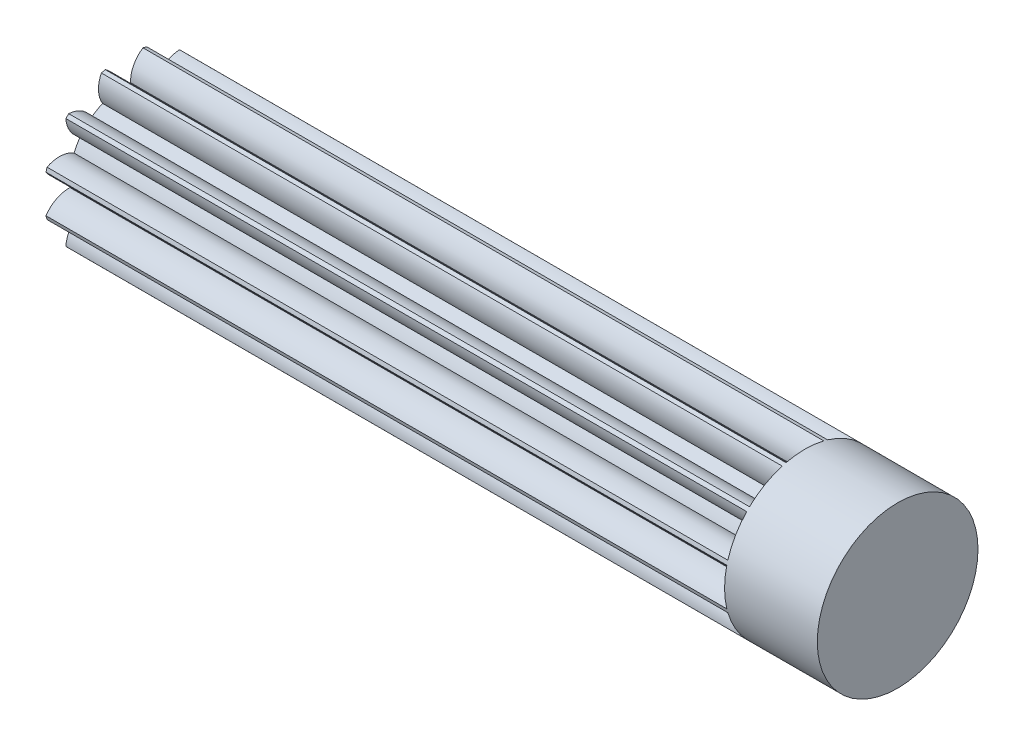
SolidWorks part; units mm, degrees
ref_plane "Plane1" through (0, 0, 0) normal (0, 0, 1) x (1, 0, 0)
ref_plane "Plane2" through (0, 0, 0) normal (0, 1, 0) x (1, 0, 0)
ref_plane "Plane3" through (0, 0, 0) normal (1, 0, 0) x (0, 0, -1)
sketch "HoldingSke" plane through (0, 0, 0) normal (0, 1, 0) x (1, 0, 0)
  line L0 (0, 0) -> (0.9781, -0.2079)
  line L1 (-15, 0) -> (100, 0) construction
  line L2 (0, 0) -> (-2.1039, 2.3779)
  line L3 (0, 0) -> (-11.863, 4.5341)
  line L4 (0, 0) -> (8.4473, 1.7955)
  line L5 (0, 0) -> (-46.8476, -17.4728)
  line L6 (0, 0) -> (-9.9476, -6.7116)
  line L7 (-2.1039, 2.3779) -> (8.6586, 51.2059)
  line L8 (-76.2, 54.61) -> (-76.1, 54.61)
  line L9 (-71.009, 38.7566) -> (-53.1078, 45.2721)
  line L10 (-76.2, 71.12) -> (104.1128, 71.12)
  line L11 (0, 0) -> (-12, 0)
  line L12 (-76.2, 101.6) -> (-76.162, 101.6)
  line L13 (24.9733, 27.94) -> (52.9518, 28.4284)
  line L14 (24.9733, 27.94) -> (24.9743, 27.94)
  line L15 (24.9733, 27.94) -> (100.4006, 29.5858)
  line L16 (-63.627, -1) -> (-12.827, -1)
  circle A0 centre (0, 0) radius 0.4
  circle A1 centre (0, 0) radius 4.749
  circle A2 centre (0, 0) radius 37.5
  circle A3 centre (0, 0) radius 0.4
  dimension "MHD" = 9.498
  dimension "Hub_dia" = 75
  dimension "Bore" = 0.8
  dimension "MBD" = 0.8
  dimension "Num_teeth" = 12
  dimension "Pitch" = 1
  dimension "Overall_len" = 50
  dimension "Show_teeth" = 12
  dimension "Thickness" = 12
  dimension "OAL" = 50.0001
  dimension "T_dim" = 0.1
  dimension "Ap" = 20
  dimension "H" = 19.05
  dimension "Pitch_radius" = 180.3128
  dimension "Width" = 12
  dimension "Backlash" = 0.038
  dimension "Addendum_fac" = 1
  dimension "Dedendum_fac" = 1.25
  dimension "Clearance_fac" = 0.25
  dimension "Dedendum_add" = 0.001
  dimension "Module" = 1
sketch "BasProSke" plane through (0, 0, 0) normal (0, 1, 0) x (1, 0, 0)
  line L0 (-10, 0) -> (60, 0) construction
  line L1 (0, 0) -> (0, 7)
  line L2 (0, 0) -> (59.315, 0)
  line L3 (59.315, 0) -> (59.315, 7)
  line L4 (59.315, 7) -> (0, 7)
  dimension "Thickness" = 59.315
  dimension "Diameter" = 14
revolve "Base-Revolve" add sketch "BasProSke" angle 360 about L0
sketch "TooCutSke" plane through (0, 0, 0) normal (1, 0, 0) x (0, 0, -1)
  line L1 (0, 0) -> (0, 107) construction
  line L2 (0, 0) -> (-0.8496, 5.9395) construction
  line L3 (0, 0) -> (-3.0836, 11.5081) construction
  line L4 (-0.8496, 5.9395) -> (-1.5418, 5.7541) construction
  arc A0 (0.5622, 4.7156) -> (-0.5622, 4.7156) centre (0, 0) ccw
  arc A1 (1.6729, 6.8233) -> (-1.6729, 6.8233) centre (0, 0) ccw
  circle A2 centre (0, 0) radius 6 construction
  circle A3 centre (0, 0) radius 5.6382 construction
  arc A4 (-0.5622, 4.7156) -> (-1.6729, 6.8233) centre (-2.9608, 4.7982) ccw
  arc A5 (1.6729, 6.8233) -> (0.5622, 4.7156) centre (2.9608, 4.7982) ccw
  dimension "Root_dia" = 9.498
  dimension "Overcut_dia" = 14.0508
  dimension "Pitch_dia" = 12
  dimension "Base_dia" = 11.2763
  dimension "Flank_rad" = 2.4
  dimension "Half_ang" = 15
  dimension "Half_CT" = 0.7167
extrude "ToothCut" cut sketch "TooCutSke" along normal through all
fillet "Breaks" [suppressed] radius 0.02 tangent propagation no
fillet "RootFillets" [suppressed] radius 0.251
pattern_circular "TeethCuts" count 12 every 30 about axis through (-10, 0, 0) along (1, 0, 0) of "ToothCut", "RootFillets", "Breaks"
sketch "HubNeaOneSke" plane through (0, 0, 0) normal (-1, 0, 0) x (0, 0, 1)
  circle A0 centre (0, 0) radius 4.749
  dimension "Diameter" = 9.498
extrude "HubNearOne" [suppressed] add sketch "HubNeaOneSke" along normal blind 10.4351
sketch "HubNeaBotSke" plane through (0, 0, 0) normal (-1, 0, 0) x (0, 0, 1)
  circle A0 centre (0, 0) radius 4.749
  dimension "Diameter" = 9.498
extrude "HubNearBoth" [suppressed] add sketch "HubNeaBotSke" along normal blind 5.2175
ref_plane "FarPln" through (59.315, 0, 0) normal (1, 0, 0) x (0, 0, -1)
sketch "HubFarSke" plane through (59.315, 0, 0) normal (1, 0, 0) x (0, 0, -1)
  circle A0 centre (0, 0) radius 4.749
  dimension "Diameter" = 9.498
extrude "HubFar" [suppressed] add sketch "HubFarSke" along normal blind 5.2175
sketch "BorSke" plane through (0, 0, 0) normal (1, 0, 0) x (0, 0, -1)
  circle A0 centre (0, 0) radius 0.4
  dimension "Diameter" = 0.8
extrude "Bore" cut sketch "BorSke" along normal mid plane 100.0001
sketch "KeySke" plane through (0, 0, 0) normal (1, 0, 0) x (0, 0, -1)
  line L0 (-0.05, 0) -> (-0.05, 0.5)
  line L1 (-0.05, 0.5) -> (0.05, 0.5)
  line L2 (0.05, 0.5) -> (0.05, 0)
  line L3 (0, 0) -> (0, 34) construction
  line L4 (-0.05, 0) -> (0.05, 0)
  dimension "Offset" = 0.5
  dimension "Width" = 0.1
extrude "Keyway" [suppressed] cut sketch "KeySke" along normal mid plane 100.0001
pattern_circular "Keyway2" [suppressed] count 2 every 90 about axis through (-10, 0, 0) along (1, 0, 0) reverse direction yes
sketch "Sketch1" plane through (0, 0, 0) normal (-1, 0, 0) x (0, 0, 1)
  circle A0 centre (0, 0) radius 7
scale "Scale1" scale about centroid uniform scaling yes scale factor 2
sketch "Sketch6" plane through (88.9537, 0, 0) normal (1, 0, 0) x (0, 0, -1)
  circle A0 centre (0, 0) radius 11.811 construction
  dimension "D1" = 23.622
sketch "Sketch9" plane through (88.9537, 0, 0) normal (1, 0, 0) x (0, 0, -1)
  circle A0 centre (0, 0) radius 14
extrude "Boss-Extrude1" add sketch "Sketch9" along normal blind 16.163
scale "Scale2" scale about centroid uniform scaling yes scale factor 0.666667
sketch "Sketch10" plane through (-6.1572, 0, 0) normal (-1, 0, 0) x (0, 0, 1)
  circle A0 centre (0, 0) radius 4
  dimension "D1" = 8
extrude "Cut-Extrude1" cut sketch "Sketch10" against normal blind 4.5
sketch "Sketch11" plane through (-1.6572, 0, 0) normal (-1, 0, 0) x (0, 0, 1)
  line L0 (1.85, 3.5465) -> (1.85, -3.5465)
  arc A4 (1.85, 3.5465) -> (1.85, -3.5465) centre (0, 0) ccw
extrude "Cut-Extrude3" cut sketch "Sketch11" against normal blind 15
equation "' \"Module@HoldingSke\" = 6.35"
equation "' \"Num_teeth@HoldingSke\" = 12"
equation "' \"Ap@HoldingSke\" =  20"
equation "' \"Ap@HoldingSke\" = 20"
equation "' \"Width@HoldingSke\" = 0.5 * 25.4"
equation "' \"Hub_dia@HoldingSke\"= 1 * 25.4"
equation "' \"Hub_dia@HoldingSke\" = 1 * 25.4"
equation "' \"Overall_len@HoldingSke\" = 1.0 * 25.4"
equation "' \"Bore@HoldingSke\" = 0.75 * 25.4"
equation "' \"T_dim@HoldingSke\" = 0.1 * 25.4"
equation "' \"Width@KeySke\" = 0.25 * 25.4"
equation "' \"Show_teeth@HoldingSke\" = 13"
equation "' \"Backlash@HoldingSke\" = 0.009 * 25.4"
equation "' \"Addendum_fac@HoldingSke\" = 1.0"
equation "' \"Dedendum_fac@HoldingSke\" = 1.25"
equation "' \"Dedendum_add@HoldingSke\" = 0.00005 * 25.4"
equation "' \"Clearance_fac@HoldingSke\" = 0.25"
equation "\"Pitch@HoldingSke\" = 1 / \"Module@HoldingSke\""
equation "\"Overcut_dia@TooCutSke\" = (\"Num_teeth@HoldingSke\" + 2 * \"Addendum_fac@HoldingSke\") / \"Pitch@HoldingSke\" + 0.002 * 25.4"
equation "\"Pitch_dia@TooCutSke\" = \"Num_teeth@HoldingSke\" / \"Pitch@HoldingSke\""
equation "\"Base_dia@TooCutSke\" = \"Num_teeth@HoldingSke\" / \"Pitch@HoldingSke\" * cos((\"Ap@HoldingSke\"  * 3.14159265 / 180))"
equation "\"Root_dia@TooCutSke\" = (\"Num_teeth@HoldingSke\" + 2) / \"Pitch@HoldingSke\" - 2 * (\"Addendum_fac@HoldingSke\" + \"Dedendum_fac@HoldingSke\") / \"Pitch@HoldingSke\" - \"Dedendum_add@HoldingSke\" * 2"
equation "\"Half_ang@TooCutSke\" = 180 / \"Num_teeth@HoldingSke\""
equation "\"Half_CT@TooCutSke\" = \"Num_teeth@HoldingSke\" / \"Pitch@HoldingSke\" * sin((3.14159265 / 2 / \"Num_teeth@HoldingSke\")) / 2 - 7 * \"Backlash@HoldingSke\" / 4"
equation "\"Flank_rad@TooCutSke\" = \"Num_teeth@HoldingSke\" / \"Pitch@HoldingSke\" / 5"
equation "\"Radius@RootFillets\" = \"Clearance_fac@HoldingSke\" / \"Pitch@HoldingSke\" + \"Dedendum_add@HoldingSke\""
equation "\"Break_rad@Breaks\" = 0.02 / \"Pitch@HoldingSke\""
equation "\"Thickness@HoldingSke\" = \"Width@HoldingSke\""
equation "\"OAL@HoldingSke\" = \"Thickness@HoldingSke\""
equation "\"MHD@HoldingSke\" = (\"Num_teeth@HoldingSke\" + 2) / \"Pitch@HoldingSke\" - 2 * (\"Addendum_fac@HoldingSke\" + \"Dedendum_fac@HoldingSke\")  / \"Pitch@HoldingSke\" - \"Dedendum_add@HoldingSke\" * 2"
equation "\"MBD@HoldingSke\" = (\"Num_teeth@HoldingSke\" + 2) / \"Pitch@HoldingSke\" - 2 * (\"Addendum_fac@HoldingSke\" + \"Dedendum_fac@HoldingSke\")  / \"Pitch@HoldingSke\" - \"Dedendum_add@HoldingSke\" * 2 - 0.002 * 25.4"
equation "\"MHD@HoldingSke\" = ((sgn( \"MHD@HoldingSke\" - \"Hub_dia@HoldingSke\" )-1)*( \"MHD@HoldingSke\" - \"Hub_dia@HoldingSke\" ))/-2+ \"Hub_dia@HoldingSke\""
equation "\"MBD@HoldingSke\" = ((sgn( \"MBD@HoldingSke\" - \"Bore@HoldingSke\" )-1)*( \"MBD@HoldingSke\" - \"Bore@HoldingSke\" ))/-2+ \"Bore@HoldingSke\""
equation "\"OAL@HoldingSke\" = ((sgn( \"OAL@HoldingSke\" - \"Overall_len@HoldingSke\" )+1)*( \"OAL@HoldingSke\" - \"Overall_len@HoldingSke\" ))/2 + \"Overall_len@HoldingSke\" + 0.000002 * 25.4"
equation "\"Num_teeth@TeethCuts\" = int( \"Show_teeth@HoldingSke\" ) + 1"
equation "\"Num_teeth@TeethCuts\" = ((sgn( \"Num_teeth@TeethCuts\" - \"Num_teeth@HoldingSke\" )-1)*( \"Num_teeth@TeethCuts\" - \"Num_teeth@HoldingSke\" ))/-2+ \"Num_teeth@HoldingSke\""
equation "\"Num_teeth@TeethCuts\" = ((sgn( \"Num_teeth@TeethCuts\" - 2.0)+1)*( \"Num_teeth@TeethCuts\" - 2.0))/2 +2.0"
equation "\"Angle@TeethCuts\" = 360.0 / \"Num_teeth@HoldingSke\""
equation "\"Diameter@BasProSke\" = (\"Num_teeth@HoldingSke\" + 2 * \"Addendum_fac@HoldingSke\") / \"Pitch@HoldingSke\""
equation "' \"Fillet_rad@BasProSke\" =  \"Thickness@HoldingSke\" * 0.05"
equation "' \"Fillet_rad@BasProSke\" = \"Thickness@HoldingSke\" * 0.05"
equation "\"MHD@HoldingSke\" = ((sgn( \"MHD@HoldingSke\" - \"Root_dia@TooCutSke\" )-1)*( \"MHD@HoldingSke\" - \"Root_dia@TooCutSke\" ))/-2+ \"Root_dia@TooCutSke\""
equation "\"Diameter@HubNeaOneSke\" = \"MHD@HoldingSke\""
equation "\"Length@HubNearOne\" = \"OAL@HoldingSke\" - \"Thickness@BasProSke\""
equation "\"Diameter@HubNeaBotSke\" = \"MHD@HoldingSke\""
equation "\"Length@HubNearBoth\" = ( \"OAL@HoldingSke\" - \"Thickness@BasProSke\" ) / 2.0"
equation "\"Thickness@FarPln\" = \"Thickness@BasProSke\""
equation "\"Diameter@HubFarSke\" = \"MHD@HoldingSke\""
equation "\"Length@HubFar\" = ( \"OAL@HoldingSke\" - \"Thickness@BasProSke\" ) / 2.0"
equation "\"Diameter@BorSke\" = \"MBD@HoldingSke\""
equation "\"D1@Bore\" = \"OAL@HoldingSke\" * 2.0"
equation "\"D1@Keyway\" = \"OAL@HoldingSke\" * 2.0"
equation "\"Offset@KeySke\" = \"T_dim@HoldingSke\" + \"MBD@HoldingSke\" / 2.0"
